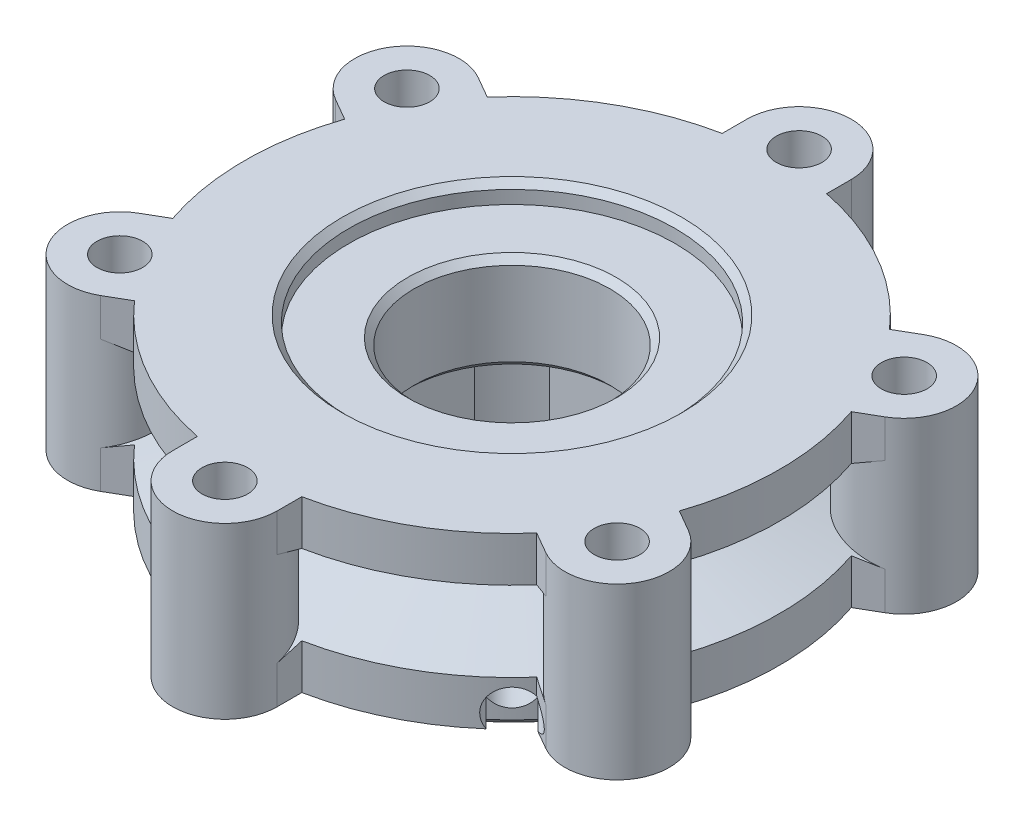
SolidWorks part; units mm, degrees
material "PLA/ABS"
ref_plane "Front Plane" through (0, 0, 0) normal (0, 0, 1) x (1, 0, 0)
ref_plane "Top Plane" through (0, 0, 0) normal (0, 1, 0) x (1, 0, 0)
ref_plane "Right Plane" through (0, 0, 0) normal (1, 0, 0) x (0, 0, -1)
other "Bounding Box"
ref_plane "Default Plane" through (13.8565, 3.175, 6.7999) normal (0, -1, 0) x (-1, 0, 0)
sketch "Sketch1" plane through (0, 0, 0) normal (0, 1, 0) x (1, 0, 0)
  line L0 (26.9408, -26.9408) -> (0, 0) construction
  line L1 (0, 0) -> (26.9408, 26.9408) construction
  line L2 (0, 0) -> (0, 38.1) construction
  circle A0 centre (0, 0) radius 38.1
  point P3 (0, 38.1)
  point P4 (38.1, 0)
  point P5 (-38.1, 0)
  point P6 (0, -38.1)
  point P7 (26.9408, 26.9408)
  point P8 (26.9408, -26.9408)
  dimension "D1" = 76.2
  dimension "D2" = 45
extrude "Boss-Extrude1" add sketch "Sketch1" along normal mid plane 16.51
ref_plane "Plane2" through (-38.1, 0, 0) normal (-1, 0, 0) x (0, 0, 1)
sketch "Sketch9" plane through (-38.1, 0, 0) normal (-1, 0, 0) x (0, 0, 1)
  line L0 (-0.635, -8.255) -> (0.635, -8.255)
  line L1 (-38.1, -8.255) -> (38.1, -8.255) construction
  line L2 (0.635, -8.255) -> (0.635, 0)
  line L3 (38.1, 8.255) -> (-38.1, 8.255) construction
  line L5 (-0.635, 0) -> (-0.635, -8.255)
  line L6 (0.635, -8.255) -> (0, -8.255) construction
  line L7 (0, -8.255) -> (0, 8.255) construction
  line L9 (-0.635, 0) -> (0.635, 0) construction
  line L10 (0.635, 0) -> (0.635, 8.255)
  line L11 (0.635, 8.255) -> (-0.635, 8.255)
  line L13 (-0.635, 8.255) -> (-0.635, 0)
  point P14 (0, 0)
  dimension "D2" = 1.27
extrude "Cut-Extrude4" cut sketch "Sketch9" against normal blind 0.635
sketch "Sketch4" plane through (0, 0, 0) normal (0, 0, 1) x (1, 0, 0)
  line L0 (-38.1, -8.255) -> (-35.56, -8.255)
  line L1 (-38.0947, -8.255) -> (38.1, -8.255) construction
  line L4 (38.1, 8.255) -> (-38.0947, 8.255) construction
  line L5 (-35.56, 8.255) -> (-38.1, 8.255)
  line L6 (-38.1, 8.255) -> (-38.1, -8.255)
  line L7 (-12.7, 0) -> (0, 0) construction
  line L8 (-35.56, -8.255) -> (-35.56, -6.6675)
  line L9 (-35.56, -6.6675) -> (-12.7, 0)
  line L10 (-12.7, 0) -> (-35.56, 6.6675)
  line L11 (-35.56, 6.6675) -> (-35.56, 8.255)
  point P17 (-38.1, 0)
  dimension "D1" = 2.54
  dimension "D2" = 25.4
  dimension "D3" = 1.5875
pattern_circular "CirPattern2" count 25 over 360 about axis through (0, -8.255, 0) along (0, 1, 0) of "Cut-Extrude4"
ref_axis "Axis1" through (0, -8.7312, 0) along (0, 1, 0)
sketch "Sketch3" plane through (0, 8.255, 0) normal (0, 1, 0) x (1, 0, 0)
  line L0 (0, 0) -> (0, 27.94) construction
  line L1 (0, 27.94) -> (0, 38.1) construction
  circle A0 centre (0, 27.94) radius 2.2225
  circle A1 centre (0, 0) radius 38.1 construction
  circle A2 centre (0, 27.94) radius 5.08
  dimension "D2" = 4.445
  dimension "D3" = 10.16
  dimension "D1" = 10.16
move or copy body "Body-Move/Copy1" [suppressed]
revolve "Cut-Revolve2" cut sketch "Sketch4" angle 360 about axis through (0, -8.7312, 0) along (0, 1, 0)
sketch "Sketch5" plane through (0, 8.255, 0) normal (0, 1, 0) x (1, 0, 0)
  circle A0 centre (0, 27.94) radius 5.08
  circle A1 centre (0, 27.94) radius 2.2225 construction
  circle A3 centre (0, 27.94) radius 2.2225
  circle A4 centre (0, 27.94) radius 5.08 construction
extrude "Boss-Extrude2" add sketch "Sketch5" against normal through all
sketch "Sketch12" plane through (0, 8.255, 0) normal (0, 1, 0) x (1, 0, 0)
  line L0 (-24.1967, 13.97) -> (0, 0) construction
  line L1 (-24.1967, -13.97) -> (-24.1967, 13.97) construction
  line L2 (-24.1967, 13.97) -> (0, 27.94) construction
  line L3 (-24.1967, -13.97) -> (0, 0) construction
  line L4 (0, 0) -> (0, 27.94) construction
  circle A0 centre (-24.1967, 13.97) radius 5.08
  circle A1 centre (0, 27.94) radius 5.08 construction
  dimension "D3" = 120
extrude "Boss-Extrude6" add sketch "Sketch12" against normal through all
sketch "Sketch17" plane through (0, 0, 0) normal (0, 1, 0) x (1, 0, 0)
  line L0 (0, 27.94) -> (0, 0) construction
  line L1 (0, 0) -> (-24.1967, 13.97) construction
  line L2 (0, 0) -> (-24.1967, -13.97) construction
  line L3 (-28.5962, -16.51) -> (-30.7959, -17.78)
  line L4 (0, 33.02) -> (0, 35.56)
  line L5 (-26.7367, -9.5706) -> (-24.6536, -8.3679)
  line L6 (-24.6536, 8.3679) -> (-26.7367, 9.5706)
  line L7 (-21.6567, 18.3694) -> (-19.5736, 17.1667)
  line L8 (-5.08, 27.94) -> (-5.08, 25.5346)
  circle A0 centre (0, 27.94) radius 5.08 construction
  circle A1 centre (-24.1967, 13.97) radius 5.08 construction
  arc A2 (0, 33.02) -> (-5.08, 27.94) centre (0, 27.94) ccw
  arc A3 (-21.6567, 18.3694) -> (-26.7367, 9.5706) centre (-24.1967, 13.97) ccw
  arc A5 (-5.08, 25.5346) -> (-19.5736, 17.1667) centre (0, 0) ccw
  circle A6 centre (0, 27.94) radius 2.2225 construction
  arc A7 (-26.7367, -9.5706) -> (-28.5962, -16.51) centre (-24.1967, -13.97) ccw
  circle A8 centre (0, 0) radius 35.56 construction
  circle A9 centre (0, 27.94) radius 2.2225
  circle A10 centre (0, 0) radius 35.56 construction
  arc A11 (0, 35.56) -> (-30.7959, -17.78) centre (0, 0) ccw
  arc A12 (-24.6536, 8.3679) -> (-24.6536, -8.3679) centre (0, 0) ccw
  circle A13 centre (-24.1967, 13.97) radius 2.2225
  circle A15 centre (-24.1967, -13.97) radius 2.2225
  dimension "D1" = 9.525
extrude "Cut-Extrude5" cut sketch "Sketch17" against normal through all both and the other way through all
pattern_circular "CirPattern1" count 3 over 360 about axis through (0, 6.6675, 0) along (0, -1, 0) of "Boss-Extrude2", "Boss-Extrude6", "Cut-Extrude5"
sketch "Sketch18" plane through (0, -8.255, 0) normal (0, -1, 0) x (1, 0, 0)
  circle A0 centre (0, 0) radius 26.035 construction
  circle A1 centre (0, 0) radius 16.51
  arc A2 (-5.08, 25.5346) -> (-19.5736, 17.1667) centre (0, 0) ccw construction
  circle A3 centre (0, 0) radius 12.7 construction
  circle A4 centre (0, 0) radius 12.7 construction
  dimension "D1" = 3.81
extrude "Boss-Extrude9" add sketch "Sketch18" against normal through all
fillet "Fillet5" radius 1.27 2 edges at (0, -1.1112, -16.51) (0, 1.1112, 16.51)
sketch "Sketch22" plane through (0, -8.255, 0) normal (0, -1, 0) x (1, 0, 0)
  circle A0 centre (0, 0) radius 22.225
  dimension "D1" = 44.45
extrude "Boss-Extrude12" add sketch "Sketch22" along normal blind 2.54
sketch "Sketch23" plane through (0, -10.795, 0) normal (0, -1, 0) x (1, 0, 0)
  line L0 (-8.5312, 8.5312) -> (-18.4095, 18.4095) construction
  line L1 (8.5312, 8.5312) -> (18.4095, 18.4095) construction
  arc A2 (24.6536, -8.3679) -> (24.6536, 8.3679) centre (0, 0) ccw construction
  arc A3 (-5.08, 25.5346) -> (-19.5736, 17.1667) centre (0, 0) ccw construction
  arc A4 (19.5736, 17.1667) -> (5.08, 25.5346) centre (0, 0) ccw construction
  point P3 (-18.2681, 18.5499)
  point P8 (0, 0)
  point P9 (0, 0)
  point P14 (18.1477, 18.6677)
  line B0 (0, -10.16) -> (-6.5068, -10.16)
  line B1 (6.5068, -10.16) -> (0, -10.16)
  line B2 (10.16, 6.5068) -> (10.16, -6.5068)
  line B3 (0, 10.16) -> (6.5068, 10.16)
  line B4 (-6.5068, 10.16) -> (0, 10.16)
  line B5 (-10.16, -6.5068) -> (-10.16, 6.5068)
  arc B6 (-10.16, -6.5068) -> (-6.5068, -10.16) centre (0, 0) ccw
  arc B7 (6.5068, -10.16) -> (10.16, -6.5068) centre (0, 0) ccw
  arc B8 (10.16, 6.5068) -> (6.5068, 10.16) centre (0, 0) ccw
  arc B9 (-6.5068, 10.16) -> (-10.16, 6.5068) centre (0, 0) ccw
sketch_block_instance "Block-BaneBots Hub-1"
sketch_block "Block-BaneBots Hub"
extrude "Cut-Extrude6" cut sketch "Sketch23" against normal blind 7.747
sketch "Sketch24" plane through (0, -3.048, 0) normal (0, -1, 0) x (1, 0, 0)
  circle A0 centre (0, 0) radius 9.525
  dimension "D1" = 19.05
extrude "Cut-Extrude7" cut sketch "Sketch24" against normal through all
sketch "Sketch25" plane through (0, 8.255, 0) normal (0, 1, 0) x (1, 0, 0)
  circle A0 centre (0, 0) radius 15.875
  dimension "D1" = 31.75
extrude "Cut-Extrude8" cut sketch "Sketch25" against normal offset from surface (1.905 mm away) 17.145 up to face at (0, -10.795, 0)
ref_plane "Plane3" through (0, 0, 0) normal (0.7071, 0, -0.7071) x (-0.7071, 0, -0.7071)
sketch "Sketch33" plane through (0, 0, 0) normal (0.7071, 0, -0.7071) x (-0.7071, 0, -0.7071)
  line L0 (0, -3.048) -> (0, -10.795) construction
  line L1 (-2.5832, -10.795) -> (2.5832, -10.795) construction
  line L2 (-2.5832, -3.048) -> (2.5832, -3.048) construction
  circle A0 centre (0, -6.9215) radius 2.2225
  dimension "D1" = 4.445
extrude "Cut-Extrude9" cut sketch "Sketch33" along normal through all
ref_plane "Plane4" through (0, 0, 0) normal (0.7071, 0, 0.7071) x (0.7071, 0, -0.7071)
sketch "Sketch34" plane through (0, 0, 0) normal (0.7071, 0, 0.7071) x (0.7071, 0, -0.7071)
  line L0 (0, -3.048) -> (0, -10.795) construction
  line L1 (-2.5832, -10.795) -> (2.5832, -10.795) construction
  line L2 (-2.5832, -3.048) -> (2.5832, -3.048) construction
  circle A0 centre (0, -6.9215) radius 2.2225
  dimension "D1" = 4.445
extrude "Cut-Extrude10" cut sketch "Sketch34" along normal through all
sketch "Sketch37" plane through (0, 0, 0) normal (0.7071, 0, -0.7071) x (-0.7071, 0, -0.7071)
  circle A0 centre (0, -6.9215) radius 3.175
  circle A1 centre (0, -6.9215) radius 2.2225
  arc A2 (1.778, -8.255) -> (-1.7019, -5.4922) centre (0, -6.9215) ccw construction
  dimension "D1" = 6.35
extrude "Boss-Extrude19" [suppressed] add sketch "Sketch37" along normal up to vertex from offset 19.05 up to point (26.9408, 0, -26.9408)
sketch "Sketch39" plane through (0, 0, 0) normal (0.7071, 0, 0.7071) x (0.7071, 0, -0.7071)
  circle A0 centre (0, -6.9215) radius 3.175
  circle A1 centre (0, -6.9215) radius 2.2225
  arc A2 (1.7019, -5.4922) -> (-1.778, -8.255) centre (0, -6.9215) ccw construction
  dimension "D1" = 6.35
extrude "Boss-Extrude20" [suppressed] add sketch "Sketch39" along normal up to vertex from offset 19.05 up to point (26.9408, 0, 26.9408)
fillet "Fillet8" [suppressed] radius 0.635
chamfer "Chamfer5" distance 0.635 angle 45 12 edges at (0, -10.795, -22.225) (0, -10.795, -10.16) (8.5312, -10.795, -8.5312) (10.16, -10.795, 0) (8.5312, -10.795, 8.5312) (0, -10.795, 10.16) (-8.5312, -10.795, 8.5312) (-10.16, -10.795, 0) (-8.5312, -10.795, -8.5312) (0, 8.255, 15.875) (0, 6.35, -9.525) (0, -3.048, -9.525)
combine bodies "Combine3" [suppressed] bodies to combine 116 169
delete or keep bodies "Body-Delete/Keep 4" [suppressed] type keep bodies bodies 117
sketch "Sketch7" [suppressed] plane through (0, -8.255, 0) normal (0, -1, 0) x (1, 0, 0)
  circle A0 centre (0, 0) radius 44.45
  circle A1 centre (0, 0) radius 38.1 construction
  dimension "D1" = 6.35
extrude "Boss-Extrude4" [suppressed] add sketch "Sketch7" against normal offset from surface (19.685 mm away) 3.175 separate body up to face at (0, 8.255, 16.51) offset beyond the face yes
combine bodies "Combine2" [suppressed] operation type subtract main body 110 bodies to subtract 114
sketch "Sketch15" [suppressed] plane through (0, 0, 0) normal (1, 0, 0) x (0, 0, -1)
  line L0 (-44.45, -8.255) -> (-49.53, -13.335)
  line L1 (-49.53, -13.335) -> (-43.18, -13.335)
  line L2 (-43.18, -13.335) -> (-38.1, -8.255)
  line L3 (-38.1, -8.255) -> (-44.45, -8.255)
  dimension "D1" = 5.08
  dimension "D2" = 45
ref_axis "Axis2" [suppressed] through (0, -9.9352, 0) along (0, 1, 0)
revolve "Revolve1" [suppressed] add sketch "Sketch15" angle 360 about axis through (0, -9.9352, 0) along (0, 1, 0)
fillet "Fillet4" [suppressed] radius 6.35
sketch "Sketch27" [suppressed] plane through (0, 11.43, 0) normal (0, 1, 0) x (1, 0, 0)
  line L0 (43.9941, 6.35) -> (50.8, 6.35)
  line L1 (50.8, -6.35) -> (43.9941, -6.35)
  line L2 (44.45, 0) -> (50.8, 0) construction
  circle A0 centre (50.8, 0) radius 1.905
  arc A1 (43.9941, -6.35) -> (43.9941, 6.35) centre (0, 0) ccw
  circle A2 centre (0, 0) radius 44.45 construction
  arc A3 (50.8, 6.35) -> (50.8, -6.35) centre (50.8, 0) cw
  dimension "D2" = 3.81
  dimension "D3" = 6.35
  dimension "D1" = 6.35
extrude "Boss-Extrude13" [suppressed] add sketch "Sketch27" against normal blind 9.525
pattern_circular "CirPattern7" [suppressed] count 3 over 360 of bodies 177
split "Split1" [suppressed] bodies to split 178
sketch "Sketch19" [suppressed] plane through (0, 11.43, 0) normal (0, 1, 0) x (1, 0, 0)
  line L0 (-43.6478, 18.0795) -> (-41.3011, 17.1075)
  line L1 (-43.6478, -18.0795) -> (-41.3011, -17.1075)
  line L2 (-47.244, 0) -> (0, 0) construction
  arc A0 (-41.3011, 17.1075) -> (-41.3011, -17.1075) centre (0, 0) ccw
  circle A1 centre (0, 0) radius 44.45 construction
  arc A2 (-43.6478, 18.0795) -> (-43.6478, -18.0795) centre (0, 0) ccw
  dimension "D2" = 2.54
  dimension "D3" = 0.254
  dimension "D1" = 45
extrude "Boss-Extrude10" [suppressed] add sketch "Sketch19" against normal blind 6.35 separate body
sketch "Sketch21" [suppressed] plane through (0, 11.43, 0) normal (0, 1, 0) x (1, 0, 0)
  line L0 (-41.3011, 17.1075) -> (-41.0664, 17.0103)
  line L1 (-41.3011, -17.1075) -> (-41.0664, -17.0103)
  line L2 (-41.3011, 17.1075) -> (-43.6478, 18.0795) construction
  line L3 (-43.6478, -18.0795) -> (-41.3011, -17.1075) construction
  arc A1 (-41.3011, 17.1075) -> (-41.3011, -17.1075) centre (0, 0) ccw construction
  arc A2 (-41.0664, 17.0103) -> (-41.0664, -17.0103) centre (0, 0) ccw
  arc A3 (-41.3011, 17.1075) -> (-41.3011, -17.1075) centre (0, 0) ccw
  circle A4 centre (0, 0) radius 44.45 construction
extrude "Boss-Extrude11" [suppressed] add sketch "Sketch21" against normal blind 3.1496
pattern_circular "CirPattern6" [suppressed] count 3 over 360 reverse direction yes of bodies 137 132
combine bodies "Combine4" [suppressed] bodies to combine 137 137 135 134
chamfer "Chamfer4" [suppressed] distance 0.635 angle 45
delete or keep bodies "Body-Delete/Keep 1" [suppressed] type delete bodies bodies 133
delete or keep bodies "Body-Delete/Keep 2" [suppressed] type delete bodies bodies 121
mirror "Mirror1" [suppressed] about plane through (0, 0, 0) normal (1, 0, 0) of bodies 121
delete or keep bodies "Body-Delete/Keep 3" [suppressed] type delete bodies bodies 121
sketch "Sketch28" [suppressed] plane through (0, 8.255, 0) normal (0, -1, 0) x (1, 0, 0)
  circle A0 centre (0, 0) radius 15.24
  dimension "D1" = 30.48
extrude "Boss-Extrude14" [suppressed] add sketch "Sketch28" along normal blind 1.27
sketch "Sketch29" [suppressed] plane through (0, 6.985, 0) normal (0, -1, 0) x (1, 0, 0)
  circle A0 centre (0, 0) radius 9.398
  dimension "D1" = 18.796
extrude "Boss-Extrude15" [suppressed] add sketch "Sketch29" along normal blind 10.16
sketch "Sketch30" [suppressed] plane through (0, -8.255, 0) normal (0, -1, 0) x (1, 0, 0)
  circle A12 centre (0, 0) radius 36.83
  circle A13 centre (0, 0) radius 34.29
  circle A14 centre (0, 0) radius 38.1 construction
  dimension "D1" = 1.27
  dimension "D2" = 2.54
extrude "Boss-Extrude16" [suppressed] add sketch "Sketch30" along normal blind 1.6002 separate body
sketch "Sketch31" [suppressed] plane through (0, -9.8552, 0) normal (0, -1, 0) x (1, 0, 0)
  line L0 (-4.1275, 27.94) -> (-4.1275, 36.598)
  line L1 (-4.1275, 36.598) -> (4.1275, 36.598)
  line L2 (4.1275, 36.598) -> (4.1275, 27.94)
  circle A0 centre (0, 27.94) radius 2.2225 construction
  circle A1 centre (0, 27.94) radius 2.2225
  arc A2 (4.1275, 27.94) -> (-4.1275, 27.94) centre (0, 27.94) cw
  circle A4 centre (0, 0) radius 36.83 construction
  dimension "D1" = 1.905
extrude "Boss-Extrude17" [suppressed] add sketch "Sketch31" against normal up to surface (1.6002 mm away) up to face at (22.272, -8.255, -15.0812)
fillet "Fillet6" [suppressed] radius 2.54
pattern_circular "CirPattern8" [suppressed] count 6 over 360 of bodies 182
sketch "Sketch32" [suppressed] plane through (0, -9.8552, 0) normal (0, -1, 0) x (1, 0, 0)
  line L0 (0, 0) -> (-2.7463, 39.2741) construction
  line L1 (2.7463, 39.2741) -> (0.7608, 36.8221)
  line L2 (0, 0) -> (0, 39.37) construction
  line L3 (-2.3026, 36.7579) -> (-2.7463, 39.2741)
  line L4 (-2.7463, 39.2741) -> (-0.7608, 36.8221)
  line L5 (-0.7608, 36.8221) -> (-2.3026, 36.7579)
  line L6 (2.3026, 36.7579) -> (2.7463, 39.2741)
  line L7 (0.7608, 36.8221) -> (2.3026, 36.7579)
  circle A0 centre (0, 0) radius 36.83 construction
  circle A1 centre (0, 0) radius 39.37 construction
  circle A2 centre (0, 0) radius 38.1 construction
  dimension "D2" = 1.27
  dimension "D1" = 6
  dimension "D3" = 35
  dimension "D4" = 4
extrude "Boss-Extrude18" [suppressed] add sketch "Sketch32" against normal up to surface (1.6002 mm away) up to face at (22.272, -8.255, -15.0812)
fillet "Fillet7" [suppressed] radius 0.635
pattern_circular "CirPattern9" [suppressed] count 10 over 360 of bodies 184
delete or keep bodies "Body-Delete/Keep 5" [suppressed] bodies 185
